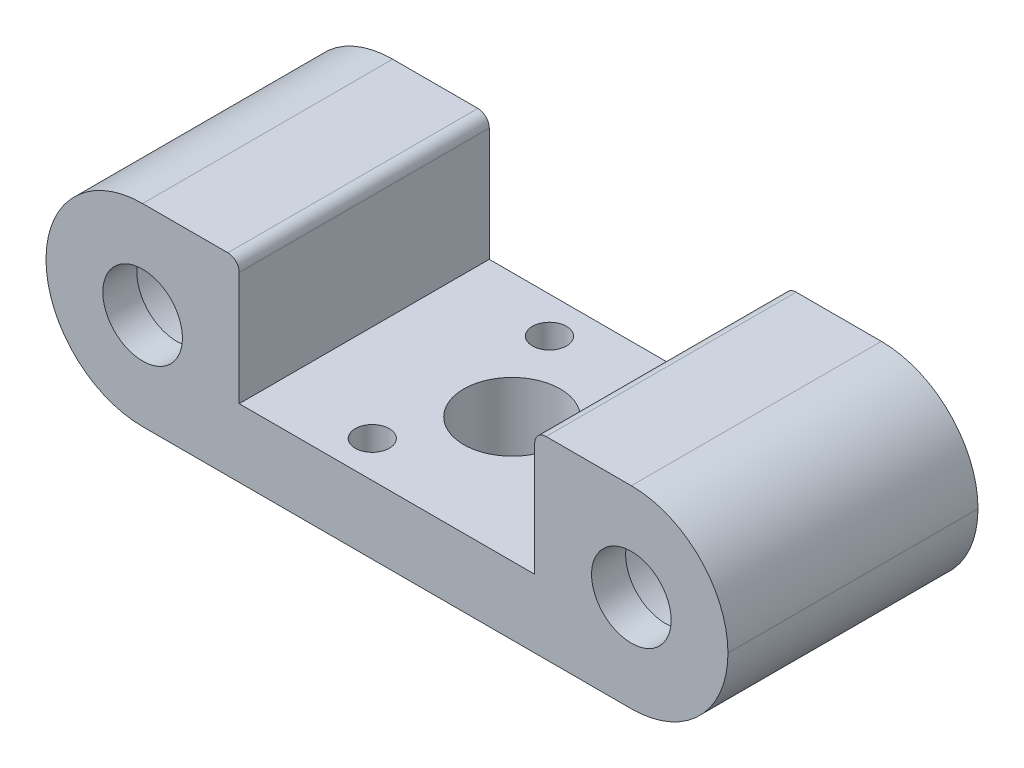
SolidWorks part; units mm, degrees
ref_plane "Plan de face" through (0, 0, 0) normal (0, 0, 1) x (1, 0, 0)
ref_plane "Plan de dessus" through (0, 0, 0) normal (0, 1, 0) x (1, 0, 0)
ref_plane "Plan de droite" through (0, 0, 0) normal (1, 0, 0) x (0, 0, -1)
sketch "Esquisse2" plane through (0, 0, 0) normal (0, 0, 1) x (1, 0, 0)
  line L0 (0, 0) -> (0, 10.2523) construction
  line L1 (-30, 0) -> (30, 0)
  line L2 (30, 0) -> (30, 17)
  line L3 (30, 17) -> (13, 17)
  line L4 (13, 17) -> (13, 6)
  line L5 (13, 6) -> (-13, 6)
  line L6 (-13, 17) -> (-13, 6)
  line L7 (-30, 17) -> (-13, 17)
  line L8 (-30, 0) -> (-30, 17)
  point P9 (0, 6)
  dimension "D1" = 6
  dimension "D2" = 17
  dimension "D3" = 17
  dimension "D4" = 26
extrude "Boss.-Extru.1" add sketch "Esquisse2" along normal blind 22
sketch "Esquisse3" plane through (0, 0, 22) normal (0, 0, 1) x (1, 0, 0)
  line L0 (21.5, 17) -> (21.5, 0) construction
  line L1 (30, 17) -> (13, 17) construction
  line L2 (-30, 0) -> (30, 0) construction
  line L3 (0, 0) -> (0, 6) construction
  line L4 (13, 6) -> (-13, 6) construction
  line L5 (-21.5, 17) -> (-21.5, 0) construction
  circle A0 centre (21.5, 8.5) radius 6.1
  circle A1 centre (-21.5, 8.5) radius 6.1
  dimension "D1" = 12.2
extrude "Enlèv. mat.-Extru.1" cut sketch "Esquisse3" against normal through all
sketch "Esquisse4" plane through (0, 0, 0) normal (0, -1, 0) x (-1, 0, 0)
  line L0 (0, 0) -> (0, -22) construction
  line L1 (30, -22) -> (-30, -22) construction
  circle A0 centre (0, -11) radius 4.25
  dimension "D1" = 8.5
extrude "Enlèv. mat.-Extru.2" cut sketch "Esquisse4" against normal through all
fillet "Congé1" radius 8.5 4 edges at (30, 0, 11) (30, 17, 11) (-30, 0, 11) (-30, 17, 11)
sketch "Esquisse5" plane through (0, 6, 0) normal (0, 1, 0) x (1, 0, 0)
  line L0 (0, -11) -> (0, 0) construction
  circle A0 centre (9, -11) radius 1.5
  circle A1 centre (-4.5, -18.7942) radius 1.5
  circle A2 centre (-4.5, -3.2058) radius 1.5
  point P12 (0, -11)
  dimension "D1" = 3
  dimension "D2" = 9
  dimension "D3" = 3
extrude "Enlèv. mat.-Extru.3" cut sketch "Esquisse5" against normal through all
sketch "Esquisse6" plane through (0, 0, 22) normal (0, 0, 1) x (1, 0, 0)
  line L0 (0, 0) -> (0, 6) construction
  line L1 (-21.5, 0) -> (21.5, 0) construction
  line L2 (13, 6) -> (-13, 6) construction
  circle A0 centre (21.5, 8.5) radius 6.25
  circle A1 centre (21.5, 8.5) radius 3.5
  circle A2 centre (-21.5, 8.5) radius 3.5
  circle A3 centre (-21.5, 8.5) radius 6.25
  dimension "D1" = 7
  dimension "D2" = 12.5
extrude "Boss.-Extru.2" add sketch "Esquisse6" against normal blind 3
fillet "Congé2" radius 1 2 edges at (-13, 17, 11) (13, 17, 11)
